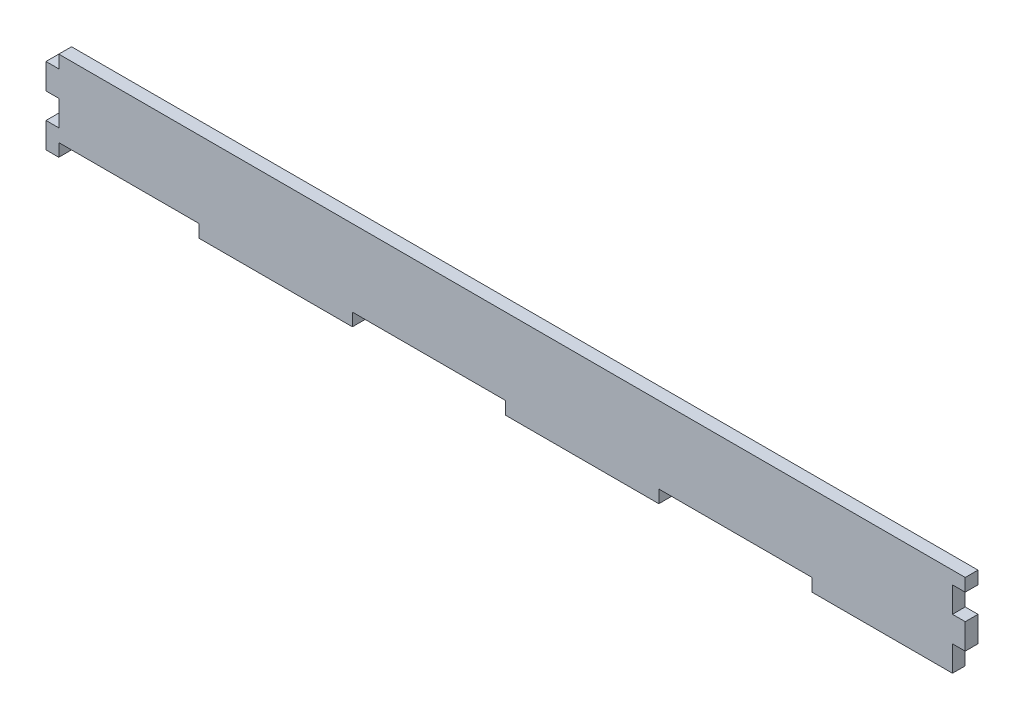
SolidWorks part; units mm, degrees
material "Acrylic (Medium-high impact)"
ref_plane "Front Plane" through (0, 0, 0) normal (0, 0, 1) x (1, 0, 0)
ref_plane "Top Plane" through (0, 0, 0) normal (0, 1, 0) x (1, 0, 0)
ref_plane "Right Plane" through (0, 0, 0) normal (1, 0, 0) x (0, 0, -1)
sketch "Sketch1" plane through (0, 0, 0) normal (0, 0, 1) x (1, 0, 0)
  line L0 (-76.2, 12.7) -> (-76.2, 9.525)
  line L1 (-114.3, 12.7) -> (114.3, 12.7)
  line L2 (-114.3, 12.7) -> (-114.3, -12.7)
  line L3 (-114.3, -12.7) -> (114.3, -12.7)
  line L4 (114.3, 12.7) -> (114.3, -12.7)
  line L5 (-114.3, 12.7) -> (-76.2, 12.7)
  line L6 (-114.3, 12.7) -> (-114.3, 9.525)
  line L7 (-114.3, 9.525) -> (-76.2, 9.525)
  line L8 (-76.2, 12.7) -> (-76.2, 9.525)
  line L9 (-76.2, 12.7) -> (-38.1, 12.7)
  line L10 (-38.1, 12.7) -> (-38.1, 9.525)
  line L11 (-76.2, 9.525) -> (-38.1, 9.525)
  line L12 (-38.1, 12.7) -> (-38.1, 9.525)
  line L13 (-38.1, 12.7) -> (0, 12.7)
  line L14 (0, 12.7) -> (0, 9.525)
  line L15 (-38.1, 9.525) -> (0, 9.525)
  line L16 (0, 12.7) -> (0, 9.525)
  line L17 (0, 12.7) -> (38.1, 12.7)
  line L18 (38.1, 12.7) -> (38.1, 9.525)
  line L19 (0, 9.525) -> (38.1, 9.525)
  line L20 (38.1, 12.7) -> (38.1, 9.525)
  line L21 (38.1, 12.7) -> (76.2, 12.7)
  line L22 (76.2, 12.7) -> (76.2, 9.525)
  line L23 (38.1, 9.525) -> (76.2, 9.525)
  line L24 (76.2, 12.7) -> (76.2, 9.525)
  line L25 (76.2, 12.7) -> (114.3, 12.7)
  line L26 (114.3, 12.7) -> (114.3, 9.525)
  line L27 (76.2, 9.525) -> (114.3, 9.525)
  line L76 (-76.2, -12.7) -> (-76.2, -9.525)
  line L77 (-114.3, -12.7) -> (-76.2, -12.7)
  line L78 (-114.3, -12.7) -> (-114.3, -9.525)
  line L79 (-114.3, -9.525) -> (-76.2, -9.525)
  line L80 (-76.2, -12.7) -> (-76.2, -9.525)
  line L81 (-76.2, -12.7) -> (-38.1, -12.7)
  line L82 (-38.1, -12.7) -> (-38.1, -9.525)
  line L83 (-76.2, -9.525) -> (-38.1, -9.525)
  line L84 (-38.1, -12.7) -> (-38.1, -9.525)
  line L85 (-38.1, -12.7) -> (0, -12.7)
  line L86 (0, -12.7) -> (0, -9.525)
  line L87 (-38.1, -9.525) -> (0, -9.525)
  line L88 (0, -12.7) -> (0, -9.525)
  line L89 (0, -12.7) -> (38.1, -12.7)
  line L90 (38.1, -12.7) -> (38.1, -9.525)
  line L91 (0, -9.525) -> (38.1, -9.525)
  line L92 (38.1, -12.7) -> (38.1, -9.525)
  line L93 (38.1, -12.7) -> (76.2, -12.7)
  line L94 (76.2, -12.7) -> (76.2, -9.525)
  line L95 (38.1, -9.525) -> (76.2, -9.525)
  line L96 (76.2, -12.7) -> (76.2, -9.525)
  line L97 (76.2, -12.7) -> (114.3, -12.7)
  line L98 (114.3, -12.7) -> (114.3, -9.525)
  line L99 (76.2, -9.525) -> (114.3, -9.525)
  line L148 (-114.3, 6.35) -> (-114.3, 0)
  line L149 (-114.3, 12.7) -> (-111.125, 12.7)
  line L150 (-114.3, 12.7) -> (-114.3, 6.35)
  line L151 (-114.3, 6.35) -> (-111.125, 6.35)
  line L152 (-111.125, 12.7) -> (-111.125, 6.35)
  line L153 (-114.3, 6.35) -> (-111.125, 6.35)
  line L154 (-111.125, 6.35) -> (-111.125, 0)
  line L155 (-114.3, 0) -> (-111.125, 0)
  line L156 (-114.3, 0) -> (-114.3, -6.35)
  line L157 (-114.3, 0) -> (-111.125, 0)
  line L158 (-111.125, 0) -> (-111.125, -6.35)
  line L159 (-114.3, -6.35) -> (-111.125, -6.35)
  line L160 (-114.3, -6.35) -> (-114.3, -12.7)
  line L161 (-114.3, -6.35) -> (-111.125, -6.35)
  line L162 (-111.125, -6.35) -> (-111.125, -12.7)
  line L163 (-114.3, -12.7) -> (-111.125, -12.7)
  line L164 (114.3, 6.35) -> (114.3, 0)
  line L165 (114.3, 12.7) -> (111.125, 12.7)
  line L166 (114.3, 12.7) -> (114.3, 6.35)
  line L167 (114.3, 6.35) -> (111.125, 6.35)
  line L168 (111.125, 12.7) -> (111.125, 6.35)
  line L169 (114.3, 6.35) -> (111.125, 6.35)
  line L170 (111.125, 6.35) -> (111.125, 0)
  line L171 (114.3, 0) -> (111.125, 0)
  line L172 (114.3, 0) -> (114.3, -6.35)
  line L173 (114.3, 0) -> (111.125, 0)
  line L174 (111.125, 0) -> (111.125, -6.35)
  line L175 (114.3, -6.35) -> (111.125, -6.35)
  line L176 (114.3, -6.35) -> (114.3, -12.7)
  line L177 (114.3, -6.35) -> (111.125, -6.35)
  line L178 (111.125, -6.35) -> (111.125, -12.7)
  line L179 (114.3, -12.7) -> (111.125, -12.7)
  point P4 (-114.3, 0)
  point P6 (0, 12.7)
  point P10 (-74.9494, 12.7)
  point P12 (-74.9494, -9.525)
  dimension "D1" = 228.6
  dimension "D2" = 25.4
  dimension "D3" = 38.1
  dimension "D4" = 3.175
  dimension "D7" = 6.35
  dimension "D8" = 3.175
  dimension "D5" = 6
  dimension "D6" = 6
  dimension "D9" = 4
  dimension "D10" = 4
extrude "Boss-Extrude1" add sketch "Sketch1" along normal blind 3.175 contours L178 L99 L94 L3 | L91 L86 L3 L90 | L83 L76 L3 L82 | L162 L79 L2 L3 | L162 L159 L2 L79 | L2 L155 L154 L151 | L175 L4 L171 L174 | L27 L168 L167 L4 | L178 L174 L170 L168 L27 L23 L19 L15 L11 L7 L152 L154 L158 L162 L79 L83 L87 L91 L95 L99 region at (0, 0, 0) region at (-112.7125, 3.175, 0) region at (-112.7125, -7.9375, 0) region at (-112.7125, -11.1125, 0) region at (112.7125, 7.9375, 0) region at (-57.15, -11.1125, 0) region at (112.7125, -3.175, 0) region at (19.05, -11.1125, 0) region at (93.6625, -11.1125, 0)
equation "\"D3@Sketch1\"=\"D1@Sketch1\"/\"D5@Sketch1\""
